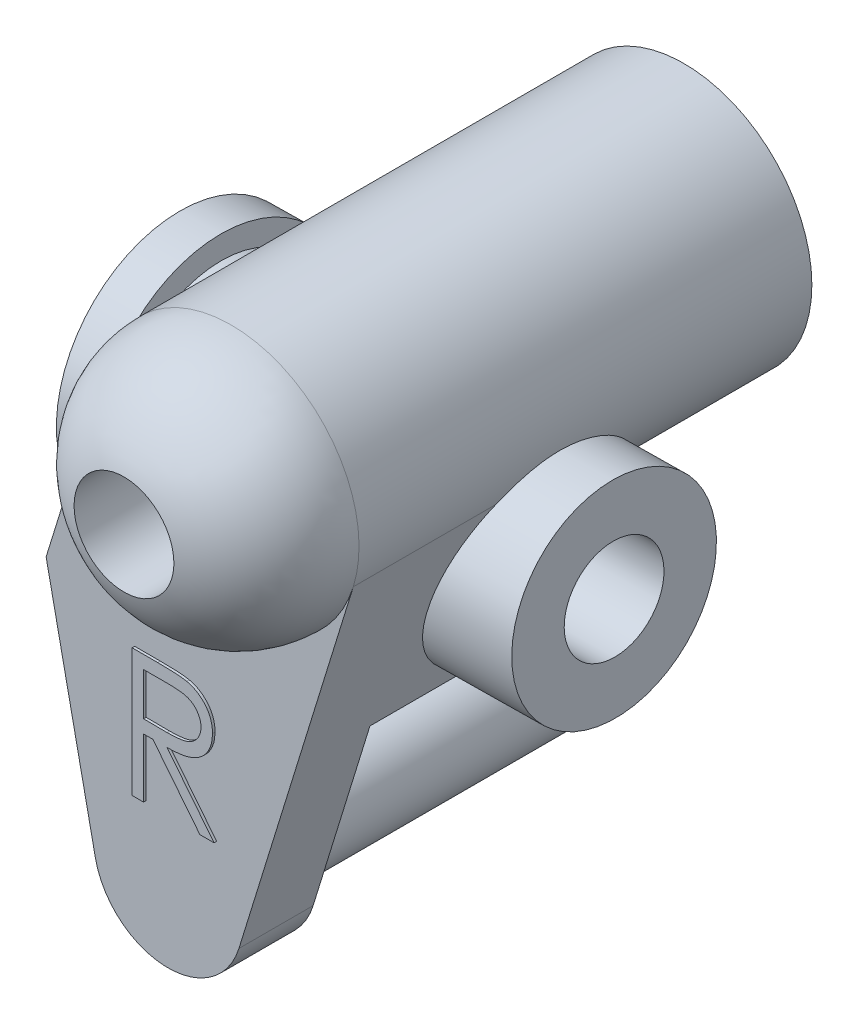
SolidWorks part; units mm, degrees
ref_plane "Plan de face" through (0, 0, 0) normal (0, 0, 1) x (1, 0, 0)
ref_plane "Plan de dessus" through (0, 0, 0) normal (0, 1, 0) x (1, 0, 0)
ref_plane "Plan de droite" through (0, 0, 0) normal (1, 0, 0) x (0, 0, -1)
sketch "Esquisse1" plane through (0, 0, 0) normal (0, 0, 1) x (1, 0, 0)
  line L0 (2.3887, -0.7377) -> (0.1525, -7.9779)
  line L1 (-2.3887, 0.7377) -> (-3.6153, -3.234)
  line L2 (-3.6153, -3.234) -> (-2.6523, -7.8464)
  arc A0 (2.3887, -0.7377) -> (-2.3887, 0.7377) centre (0, 0) ccw
  arc A1 (-2.6523, -7.8464) -> (0.1525, -7.9779) centre (-1.2329, -7.55) ccw
  dimension "D1" = 5
  dimension "D2" = 2.9
  dimension "D3" = 7.55
  dimension "D4" = 7.65
  dimension "D5" = 4.2
extrude "Boss.-Extru.1" add sketch "Esquisse1" along normal blind 1.45
sketch "Esquisse2" plane through (0, 0, 1.45) normal (0, 0, 1) x (1, 0, 0)
  circle A0 centre (0, 0) radius 2.5
  arc A1 (2.3887, -0.7377) -> (-2.3887, 0.7377) centre (0, 0) ccw construction
extrude "Boss.-Extru.2" add sketch "Esquisse2" along normal blind 2.2
sketch "Esquisse3" plane through (0, 0, 3.65) normal (0, 0, 1) x (1, 0, 0)
  circle A0 centre (0, 0) radius 2.5
  arc A1 (2.3887, -0.7377) -> (-2.3887, 0.7377) centre (0, 0) ccw construction
extrude "Boss.-Extru.3" add sketch "Esquisse3" against normal blind 11.05
sketch "Esquisse4" plane through (0, 0, 0) normal (0, 0, -1) x (-1, 0, 0)
  circle A0 centre (1.2329, -7.55) radius 0.95
  dimension "D1" = 1.9
extrude "Boss.-Extru.4" add sketch "Esquisse4" along normal blind 7.5 from surface starting at face at (-1.8119, -4.2082, 1.45)
fillet "Congé1" radius 2.2 1 edges at (2.5, 0, 3.65)
ref_plane "Plan1" through (2.4997, 0.0365, 0) normal (0.9999, 0.0146, 0) x (0, 0, -1)
sketch "Esquisse5" plane through (2.4997, 0.0365, 0) normal (0.9999, 0.0146, 0) x (0, 0, -1)
  line L0 (7.4, -2.5) -> (7.4, 2.5) construction
  line L1 (7.4, 2.5) -> (-1.45, 2.5) construction
  line L2 (2.5, -4.4) -> (0, -4.4)
  line L3 (0, -7.9793) -> (0, -0.7725) construction
  line L4 (0, -4.4) -> (0, 1.4428)
  line L5 (0, 1.4428) -> (2.5, 1.4428)
  line L6 (2.5, 1.4428) -> (2.5, -0.4)
  arc A0 (2.5, -4.4) -> (2.5, -0.4) centre (2.5, -2.4) ccw
  dimension "D1" = 4
  dimension "D2" = 4.9
  dimension "D3" = 4.9
extrude "Boss.-Extru.5" add sketch "Esquisse5" along normal blind 1 and the other way blind 7.454
sketch "Esquisse7" plane through (0, 0, 0) normal (0, 0, 1) x (1, 0, 0)
  line L0 (-2.0625, 1.4128) -> (-4.9745, 1.3703)
  line L1 (-4.9745, 1.3703) -> (-4.8892, -4.4719)
  line L2 (-4.8892, -4.4719) -> (-3.3615, -4.4496)
  line L3 (-3.3615, -4.4496) -> (-3.6153, -3.234)
  line L4 (-3.6153, -3.234) -> (-2.3887, 0.7377)
  line L5 (1.2631, -4.382) -> (3.5639, -4.3484)
  line L6 (3.5639, -4.3484) -> (3.4786, 1.4937)
  line L7 (3.4786, 1.4937) -> (2.0204, 1.4724)
  line L8 (2.3887, -0.7377) -> (1.2631, -4.382)
  arc A0 (-2.0625, 1.4128) -> (-2.3887, 0.7377) centre (0, 0) ccw
  arc A1 (2.0204, 1.4724) -> (2.3887, -0.7377) centre (0, 0) cw
extrude "Enlèv. mat.-Extru.2" cut sketch "Esquisse7" against normal blind 6
sketch "Esquisse8" plane through (2.4997, 0.0365, 0) normal (0.9999, 0.0146, 0) x (0, 0, -1)
  circle A0 centre (2.5, -2.4) radius 2
  arc A1 (2.5, -4.4) -> (3.6625, -0.7725) centre (2.5, -2.4) ccw construction
extrude "Boss.-Extru.6" add sketch "Esquisse8" along normal blind 1 and the other way blind 7.45
sketch "Esquisse9" plane through (-4.9495, -0.0723, 0) normal (-0.9999, -0.0146, 0) x (0, 0, 1)
  circle A0 centre (-2.5, -2.4) radius 2.45
  dimension "D1" = 4.9
extrude "Boss.-Extru.7" add sketch "Esquisse9" against normal blind 0.8
sketch "Esquisse10" plane through (0, 0, -6.05) normal (0, 0, -1) x (-1, 0, 0)
  circle A0 centre (1.2329, -7.55) radius 3.6
  circle A1 centre (1.2329, -7.55) radius 0.95
  circle A2 centre (1.2329, -7.55) radius 0.95 construction
  dimension "D1" = 7.2
extrude "Enlèv. mat.-Extru.3" cut sketch "Esquisse10" against normal up to surface (6.05 mm away) up to face at (-0.2829, -7.55, 0)
sketch "Esquisse11" plane through (0, 0, -7.4) normal (0, 0, -1) x (-1, 0, 0)
  circle A0 centre (0, 0) radius 0.975
  dimension "D1" = 1.95
extrude "Enlèv. mat.-Extru.4" cut sketch "Esquisse11" against normal blind 14.8
sketch "Esquisse12" plane through (-4.9495, -0.0723, 0) normal (-0.9999, -0.0146, 0) x (0, 0, 1)
  circle A0 centre (-2.5, -2.4) radius 0.975
  dimension "D1" = 1.95
extrude "Enlèv. mat.-Extru.5" cut sketch "Esquisse12" against normal blind 14.8
sketch "Esquisse13" plane through (0, 0, 1.45) normal (0, 0, 1) x (1, 0, 0)
  text T0 "R" font "Century Gothic" height 2.5
extrude "Boss.-Extru.8" add sketch "Esquisse13" along normal blind 0.05
scale "Scale1" scale about centroid uniform scaling yes scale factor 6.5
